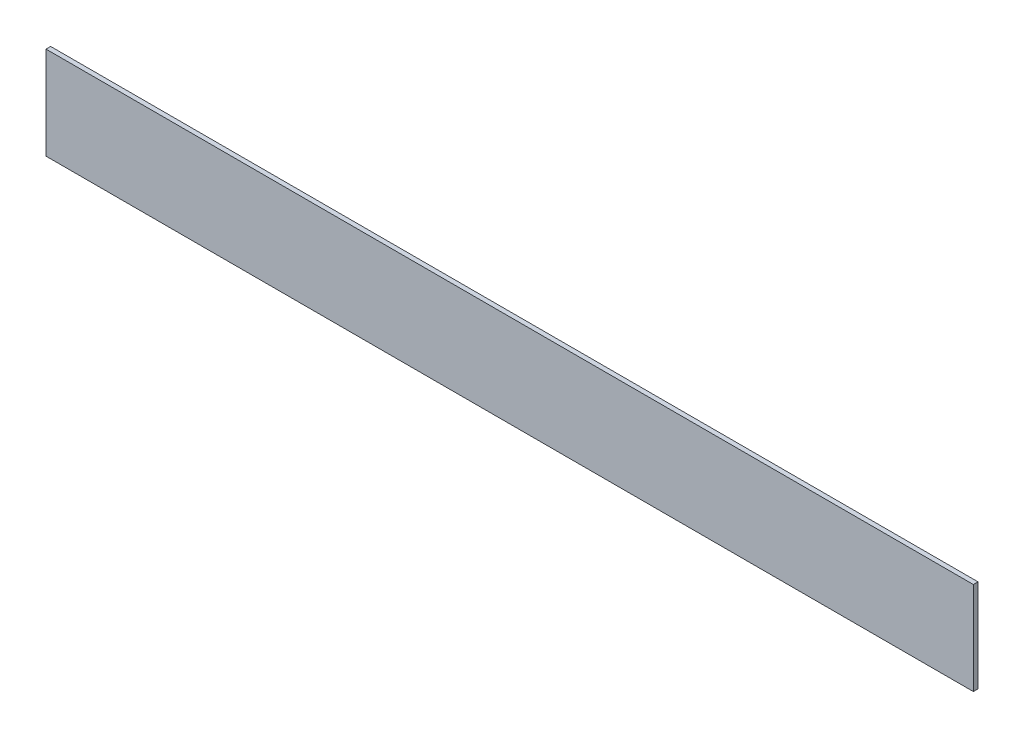
SolidWorks part; units mm, degrees
ref_plane "Ön Düzlem" through (0, 0, 0) normal (0, 0, 1) x (1, 0, 0)
ref_plane "Üst Düzlem" through (0, 0, 0) normal (0, 1, 0) x (1, 0, 0)
ref_plane "Sağ Düzlem" through (0, 0, 0) normal (1, 0, 0) x (0, 0, -1)
sketch "Çizim1" plane through (0, 0, 0) normal (0, 0, 1) x (1, 0, 0)
  line L1 (0, 0) -> (1000, 0)
  line L2 (0, 0) -> (0, -100)
  line L3 (0, -100) -> (1000, -100)
  line L4 (1000, 0) -> (1000, -100)
  dimension "D1" = 1000
  dimension "D2" = 100
base flange "Taban-Flanş1" sketch "Çizim1" thickness 5 reverse thickness direction no parameters "D1"=6
sketch "Büküm-Çizgileri1" [suppressed] plane through (0, 0, 0) normal (0, 1, 0) x (1, 0, 0)
sketch "Sınırlandırma-Kutusu1" [suppressed] plane through (0, 0, 0) normal (0, 1, 0) x (1, 0, 0)
sheet metal parameters "Sac-Levha1" thickness 5 parameters "D1"=6
flat pattern "Düz-Çoğaltma1" [suppressed]
sketch "Büküm-Çizgileri2" plane through (0, 0, 0) normal (0, 1, 0) x (1, 0, 0)
sketch3d "Sınırlandırma-Kutusu2" [suppressed]
  line L0 (0, -100, 0) -> (1000, -100, 0) construction
  line L1 (0, 0, 0) -> (1000, 0, 0) construction
  line L2 (0, -100, 0) -> (0, 0, 0) construction
  line L3 (1000, -100, 0) -> (1000, 0, 0) construction
